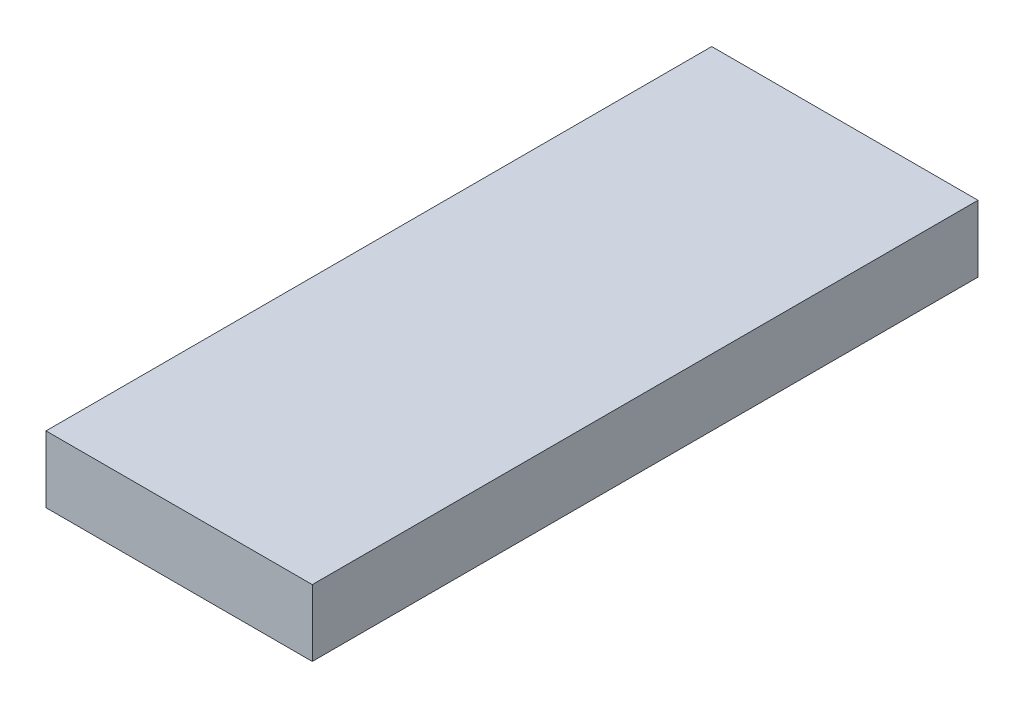
SolidWorks part; units mm, degrees
material "Maple"
ref_plane "Front Plane" through (0, 0, 0) normal (0, 0, 1) x (1, 0, 0)
ref_plane "Top Plane" through (0, 0, 0) normal (0, 1, 0) x (1, 0, 0)
ref_plane "Right Plane" through (0, 0, 0) normal (1, 0, 0) x (0, 0, -1)
sketch "Sketch1" plane through (0, 0, 0) normal (0, 1, 0) x (1, 0, 0)
  line L0 (0, 0) -> (50.8, 0)
  line L1 (0, 0) -> (0, 127)
  line L2 (50.8, 0) -> (50.8, 127)
  line L3 (0, 127) -> (50.8, 127)
  dimension "D1" = 50.8
  dimension "D2" = 127
extrude "Boss-Extrude1" add sketch "Sketch1" along normal blind 12.7
